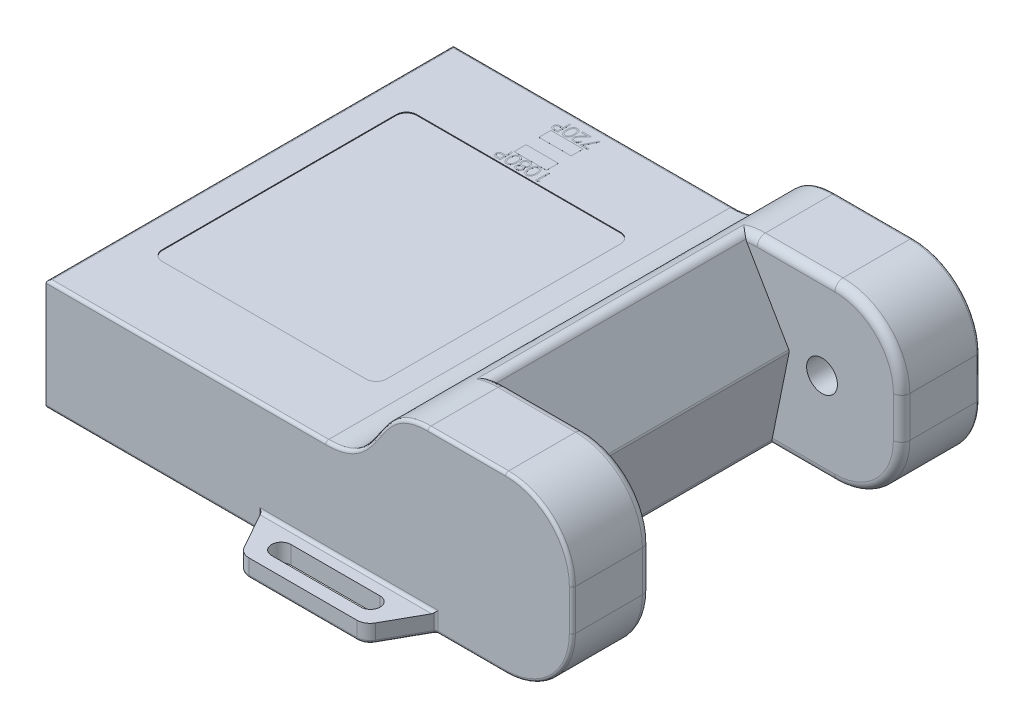
SolidWorks part; units mm, degrees
note: The reader was unsure of these and kept them because the rebuilt part matched: shared geometry of "Sketch4<3>".
ref_plane "Front" through (0, 0, 0) normal (0, 0, 1) x (1, 0, 0)
ref_plane "Top" through (0, 0, 0) normal (0, 1, 0) x (1, 0, 0)
ref_plane "Right" through (0, 0, 0) normal (1, 0, 0) x (0, 0, -1)
sketch "Sketch1" plane through (0, 0, 0) normal (0, 1, 0) x (1, 0, 0)
  line L1 (-26.035, -20.1486) -> (26.035, -20.1486)
  line L2 (-26.035, -20.1486) -> (-26.035, 20.1486)
  line L3 (-26.035, 20.1486) -> (26.035, 20.1486)
  line L4 (26.035, -20.1486) -> (26.035, 20.1486)
  line L5 (-26.035, -20.1486) -> (26.035, 20.1486) construction
  line L6 (-26.035, 20.1486) -> (26.035, -20.1486) construction
  point P0 (0, 0)
  dimension "D1" = 52.07
  dimension "D2" = 40.2971
extrude "Boss-Extrude1" add sketch "Sketch1" along normal mid plane 17.2314
sketch "Sketch2" plane through (0, 0, 20.1486) normal (0, 0, 1) x (1, 0, 0)
  line L0 (-26.035, 2.4079) -> (1.6276, 2.4079)
  line L1 (-26.035, 8.6157) -> (-26.035, -8.6157) construction
  line L2 (-26.035, -8.6157) -> (26.035, -8.6157) construction
  line L3 (-26.035, 8.6157) -> (26.035, 8.6157) construction
  line L4 (26.035, 8.6157) -> (26.035, -8.6157) construction
  spline S0 degree 3 poles (1.6276, 2.4079) (7.5884, 2.4079) (5.8598, 8.6157) (11.7475, 8.6157) knots 0 0 0 0 1 1 1 1
  dimension "D1" = 11.0236
  dimension "D2" = 14.2875
extrude "Cut-Extrude1" cut sketch "Sketch2" against normal through all
fillet "Fillet1" radius 6.604 2 edges at (26.035, -8.6157, 0) (26.035, 8.6157, 0)
sketch "Sketch3" plane through (-26.035, 0, 0) normal (-1, 0, 0) x (0, 0, 1)
  line L0 (20.1486, 2.4079) -> (-20.1485, 2.4079) construction
  line L1 (7.0168, 0.1981) -> (18.4468, 0.1981)
  line L2 (7.0168, 0.1981) -> (7.0168, -3.5357)
  line L3 (7.0168, -3.5357) -> (18.4468, -3.5357)
  line L4 (18.4468, 0.1981) -> (18.4468, -3.5357)
  line L5 (20.1486, 2.4079) -> (20.1486, -8.6157) construction
  dimension "D1" = 11.43
  dimension "D2" = 3.7338
  dimension "D3" = 2.2098
  dimension "D4" = 1.7018
extrude "Cut-Extrude2" cut sketch "Sketch3" against normal blind 2.54
sketch "Sketch4" plane through (-23.495, 0, 0) normal (-1, 0, 0) x (0, 0, 1)
  line L0 (18.4468, 0.1981) -> (7.0168, 0.1981) construction
  line L1 (7.5248, -0.0559) -> (17.9388, -0.0559)
  line L2 (7.5248, -0.0559) -> (7.5248, -3.2817)
  line L3 (7.5248, -3.2817) -> (17.9388, -3.2817)
  line L4 (17.9388, -0.0559) -> (17.9388, -3.2817)
  line L5 (18.4468, 0.1981) -> (7.0168, 0.1981) construction
  line L6 (7.0168, -3.5357) -> (18.4468, -3.5357) construction
  line L7 (8.0328, -0.5639) -> (17.4308, -0.5639)
  line L8 (17.4308, -0.5639) -> (17.4308, -2.7737)
  line L9 (8.0328, -2.7737) -> (17.4308, -2.7737)
  line L10 (8.0328, -0.5639) -> (8.0328, -2.7737)
  line L11 (12.7318, -3.2817) -> (12.7318, -2.7737) construction
  line L12 (15.7917, -2.7737) -> (15.7917, -3.2817)
  line L13 (9.5448, -2.7737) -> (9.6718, -2.7737)
  line L14 (9.5448, -2.7737) -> (9.5448, -3.2817)
  line L15 (9.5448, -3.2817) -> (9.6718, -3.2817)
  line L16 (9.6718, -2.7737) -> (9.6718, -3.2817)
  line L17 (15.9187, -3.2817) -> (15.7917, -3.2817)
  line L18 (15.9187, -2.7737) -> (15.9187, -3.2817)
  line L19 (15.9187, -2.7737) -> (15.7917, -2.7737)
  point P4 (12.7318, -0.0559)
  point P7 (12.7318, 0.1981)
  point P22 (9.6718, -3.0277)
  dimension "D1" = 10.414
  dimension "D2" = 0.254
  dimension "D3" = 0.254
  dimension "D5" = 0.127
  dimension "D4" = 0.508
extrude "Boss-Extrude2" add sketch "Sketch4" along normal offset from surface (2.4892 mm away) 0.0508 contours L9 L18 L3 L4 L1 L2 L14 L10 L7 L8 | L3 L11 L9 L16 | L11 L3 L12 L9 up to face at (-26.035, -1.6688, 12.7318)
extrude "Boss-Extrude3" add sketch "Sketch4<3>" along normal blind 1.0668 contours L18 L9 L12 L3 | L16 L9 L14 L3
sketch "Sketch4<3>" plane through (-23.495, 0, 0) normal (-1, 0, 0) x (0, 0, 1) same geometry as "Sketch4"
sketch "Sketch6" plane through (-23.495, 0, 0) normal (-1, 0, 0) x (0, 0, 1)
  circle A0 centre (8.8739, -1.9608) radius 0.127
  circle A1 centre (10.1439, -1.9608) radius 0.127
  circle A2 centre (11.4139, -1.9608) radius 0.127
  circle A3 centre (12.6839, -1.9608) radius 0.127
  circle A4 centre (13.9539, -1.9608) radius 0.127
  circle A5 centre (15.2239, -1.9608) radius 0.127
  circle A6 centre (16.4939, -1.9608) radius 0.127
  dimension "D1" = 0.254
  dimension "D2" = 7
extrude "Boss-Extrude4" add sketch "Sketch6" along normal offset from surface (1.524 mm away) 1.016 up to face at (-26.035, -1.6688, 12.7318)
fillet "Fillet2" radius 0.254 4 edges at (-24.7396, -0.0559, 17.9388) (-24.7396, -3.2817, 17.9388) (-24.7396, -3.2817, 7.5248) (-24.7396, -0.0559, 7.5248)
fillet "Fillet3" radius 0.127 4 edges at (-24.765, 0.1981, 18.4468) (-24.765, -3.5357, 18.4468) (-24.765, -3.5357, 7.0168) (-24.765, 0.1981, 7.0168)
sketch "Sketch7" plane through (-26.035, 0, 0) normal (-1, 0, 0) x (0, 0, 1)
  line L0 (-20.1486, -8.6157) -> (20.1486, -8.6157) construction
  line L1 (-3.0226, -5.6693) -> (3.0226, -5.6693)
  line L2 (-3.0226, -5.6693) -> (-3.0226, -2.7991)
  line L3 (-3.0226, -2.7991) -> (3.0226, -2.7991)
  line L4 (3.0226, -5.6693) -> (3.0226, -2.7991)
  line L5 (-3.0226, -5.6693) -> (3.0226, -2.7991) construction
  line L6 (-3.0226, -2.7991) -> (3.0226, -5.6693) construction
  point P0 (0, -4.2342)
  dimension "D1" = 6.0452
  dimension "D2" = 2.8702
  dimension "D3" = 2.9464
extrude "Boss-Extrude5" add sketch "Sketch7" along normal blind 0.8382 separate body
fillet "Fillet4" radius 0.0508 8 edges at (-26.8732, -5.6693, 0) (-26.8732, -4.2342, -3.0226) (-26.8732, -2.7991, 0) (-26.8732, -4.2342, 3.0226) (-26.4541, -2.7991, -3.0226) (-26.4541, -5.6693, 3.0226) (-26.4541, -5.6693, -3.0226) (-26.4541, -2.7991, 3.0226)
sketch "Sketch8" plane through (0, -8.6157, 0) normal (0, -1, 0) x (1, 0, 0)
  line L0 (-26.035, 20.1486) -> (19.431, 20.1486) construction
  line L1 (-2.1844, 24.6951) -> (10.033, 24.6951)
  line L2 (-2.1844, 24.6951) -> (-2.1844, 20.1486)
  line L3 (-2.1844, 20.1486) -> (10.033, 20.1486)
  line L4 (10.033, 24.6951) -> (10.033, 20.1486)
  line L5 (-2.1844, 24.6951) -> (-4.7244, 20.1486)
  line L6 (3.9243, 24.6951) -> (3.9243, 20.1486) construction
  line L7 (-4.7244, 20.1486) -> (-2.1844, 20.1486)
  line L8 (12.573, 20.1486) -> (10.033, 20.1486)
  line L9 (10.033, 24.6951) -> (12.573, 20.1486)
  line L10 (26.035, 20.1486) -> (26.035, -20.1486) construction
  line L11 (-0.489, 22.4218) -> (8.3375, 22.4218) construction
  line L12 (-0.489, 23.3744) -> (8.3375, 23.3744)
  line L13 (-0.489, 21.4693) -> (8.3375, 21.4693)
  line L14 (0, 0) -> (26.035, 0) construction
  line L15 (-2.1844, 24.6951) -> (-4.7244, 20.1486)
  line L16 (-4.7244, 20.1486) -> (-2.1844, 20.1486)
  line L17 (12.573, 20.1486) -> (10.033, 20.1486)
  line L18 (10.033, 24.6951) -> (12.573, 20.1486)
  line L19 (-2.1844, 24.6951) -> (-2.1844, 20.1486)
  line L20 (10.033, 24.6951) -> (10.033, 20.1486)
  line L21 (12.573, 20.1486) -> (10.033, 20.1486)
  line L22 (10.033, 24.6951) -> (12.573, 20.1486)
  line L23 (-2.1844, 24.6951) -> (-2.1844, 20.1486)
  line L24 (10.033, 24.6951) -> (10.033, 20.1486)
  line L25 (-2.1844, 24.6951) -> (-4.7244, 20.1486)
  line L26 (-4.7244, 20.1486) -> (-2.1844, 20.1486)
  line L27 (-2.1844, 24.6951) -> (-4.7244, 20.1486)
  line L28 (-4.7244, 20.1486) -> (-2.1844, 20.1486)
  line L29 (-2.1844, 24.6951) -> (-2.1844, 20.1486)
  line L30 (10.033, 24.6951) -> (10.033, 20.1486)
  arc A0 (-0.489, 23.3744) -> (-0.489, 21.4693) centre (-0.489, 22.4218) ccw
  arc A1 (8.3375, 21.4693) -> (8.3375, 23.3744) centre (8.3375, 22.4218) ccw
  point P14 (3.9243, 22.4218)
  point P19 (9.29, 22.4218)
  point P20 (-1.4415, 22.4218)
  line M9 (19.431, 20.1486) -> (-26.035, 20.1486)
  dimension "D1" = 4.5466
  dimension "D2" = 12.2174
  dimension "D3" = 2.54
  dimension "D4" = 13.462
  dimension "D5" = 10.7315
  dimension "D6" = 1.905
extrude "Boss-Extrude6" add sketch "Sketch8" against normal blind 1.778 contours L2 L5 M9 | L4 L1 L2 A1 L13 A0 L12 M9 | L9 L4 M9
mirror "Mirror1" about plane through (0, 0, 0) normal (0, 0, 1) of "Boss-Extrude6"
fillet "Fillet5" radius 1.3208 4 edges at (-2.1844, -7.7267, -24.6951) (10.033, -7.7267, -24.6951) (-2.1844, -7.7267, 24.6951) (10.033, -7.7267, 24.6951)
fillet "Fillet6" radius 0.3048 6 edges at (12.573, -7.7267, -20.1486) (3.9243, -6.8377, -20.1486) (-4.7244, -7.7267, -20.1486) (12.573, -7.7267, 20.1486) (-4.7244, -7.7267, 20.1486) (3.9243, -6.8377, 20.1486)
sketch "Sketch9" plane through (0, 8.6157, 0) normal (0, 1, 0) x (1, 0, 0)
  line L0 (26.035, 20.1486) -> (26.035, -20.1486) construction
  line L1 (26.035, 12.4143) -> (14.9352, 12.4142)
  line L2 (26.035, 12.4143) -> (26.035, -12.4143)
  line L3 (26.035, -12.4143) -> (14.9352, -12.4142)
  line L4 (14.9352, 12.4142) -> (14.9352, -12.4142)
  line L5 (11.7475, -20.1486) -> (11.7475, 20.1485) construction
  line L6 (26.035, 20.1486) -> (19.431, 20.1486) construction
  point P6 (14.9352, 0)
  point P9 (11.7475, 0)
  dimension "D1" = 7.7343
  dimension "D2" = 11.0998
extrude "Cut-Extrude3" cut sketch "Sketch9" against normal up to next
sketch "Sketch10" plane through (0, 0, -12.4142) normal (0, 0, 1) x (1, 0, 0)
  line L0 (14.9352, 0.4877) -> (10.287, 8.4639)
  line L1 (14.9352, -8.6157) -> (14.9352, 8.6157) construction
  line L2 (19.431, 8.6157) -> (14.9352, 8.6157) construction
  line L3 (26.035, 2.0117) -> (26.035, -2.0117) construction
  line L4 (14.9352, 0.4877) -> (14.9352, 8.6157)
  line L5 (14.9352, 0.4877) -> (13.081, -8.6157)
  line L6 (-26.035, -8.6157) -> (-4.9033, -8.6157) construction
  line L7 (10.287, 8.4639) -> (10.287, 11.5298)
  line L8 (10.287, 11.5298) -> (14.9352, 11.5298)
  line L9 (14.9352, 8.4639) -> (14.9352, 11.5298)
  line L10 (-26.035, 2.4079) -> (-26.035, -8.6157) construction
  line L11 (14.9352, 0.4877) -> (14.9352, -8.6157)
  line L14 (13.081, -8.6157) -> (13.081, -10.4697)
  line L15 (13.081, -10.4697) -> (14.9352, -10.4697)
  line L16 (14.9352, -8.6157) -> (14.9352, -10.4697)
  spline S0 degree 3 poles (1.6276, 2.4079) (7.5884, 2.4079) (5.8598, 8.6157) (11.7475, 8.6157) knots 0 0 0 0 1 1 1 1 construction
  line M8 (14.9352, 8.6157) -> (14.9352, -8.6157)
  dimension "D1" = 8.128
  dimension "D2" = 15.748
  dimension "D3" = 39.116
extrude "Cut-Extrude4" cut sketch "Sketch10" along normal up to surface (24.8285 mm away) contours L9 L8 L7 L0 L4 M8 | L16 L5 L14 L15 M8 up to face at (20.5896, 0, 12.4143)
fillet "Fillet7" radius 0.8128 14 edges at (13.081, -8.6157, 0) (10.287, 8.4639, 0) (16.256, -8.6157, 12.4143) (24.1007, -6.6814, 12.4143) (26.035, 0, 12.4143) (24.1007, 6.6814, 12.4143) (16.256, -8.6157, -12.4142) (24.1007, -6.6814, -12.4142) (26.035, 0, -12.4143) (24.1007, 6.6814, -12.4142) (15.5892, 8.6157, 12.4143) (15.5892, 8.6157, -12.4142)
fillet "Fillet8" radius 0.3048 1 edges at (14.9352, 0.4877, 0)
fillet "Fillet9" radius 0.3048 32 edges at (15.5892, 8.6157, 20.1486) (-12.2037, 2.4079, -20.1485) (-12.2037, 2.4079, 20.1486) (-26.035, 2.4079, 0) (26.035, 0, -20.1486) (26.035, 0, 20.1486) (15.5892, 8.6157, -20.1485) (3.9243, -8.6157, -24.6951) (11.4484, -8.6157, 22.1616) (3.9243, -8.6157, 24.6951) (16.0914, -8.6157, -20.1486) (-3.5998, -8.6157, 22.1616) (-3.5998, -8.6157, -22.1616) (11.4484, -8.6157, -22.1616) (9.9264, -8.6157, 24.5135) (24.1007, 6.6814, -20.1486) (-2.0778, -8.6157, 24.5135) (-2.0778, -8.6157, -24.5135) (9.9264, -8.6157, -24.5135) (24.1007, -6.6814, -20.1486) (24.1007, 6.6814, 20.1486) (24.1007, -6.6814, 20.1486) (-15.4691, -8.6157, -20.1486) (16.0914, -8.6157, 20.1486) (12.5976, -8.6157, -20.1905) (-4.749, -8.6157, -20.1905) (12.5976, -8.6157, 20.1905) (-4.749, -8.6157, 20.1905) (-15.4691, -8.6157, 20.1486) (-26.035, -8.6157, 0)
sketch "Sketch11" plane through (0, 0, 0) normal (0, 0, 1) x (1, 0, 0)
  line L0 (26.035, 2.0117) -> (26.035, -2.0117) construction
  line L1 (25.7302, -2.0117) -> (25.7302, 2.0117) construction
  circle A0 centre (18.161, 0) radius 1.524
  point P6 (25.7302, 0)
  dimension "D1" = 3.048
  dimension "D2" = 7.874
extrude "Cut-Extrude5" cut sketch "Sketch11" against normal offset from surface 2.54 and the other way offset from surface (14.9543 mm away) 2.54 up to face at (17.5268, 0.9697, -12.4142) offset beyond the face yes other way up to face at (17.4126, 0.9607, 12.4142)
sketch "Sketch12" plane through (0, 2.4079, 0) normal (0, 1, 0) x (1, 0, 0)
  line L0 (-26.035, 20.1486) -> (1.6276, 20.1486) construction
  line L1 (-13.8557, 17.6086) -> (-10.6553, 17.6086)
  line L2 (-13.8557, 17.6086) -> (-13.8557, 16.4275)
  line L3 (-13.8557, 16.4275) -> (-10.6553, 16.4275)
  line L4 (-10.6553, 17.6086) -> (-10.6553, 16.4275)
  line L5 (-13.8557, 15.1574) -> (-10.6553, 15.1574)
  line L6 (-13.8557, 15.1574) -> (-13.8557, 13.9763)
  line L7 (-13.8557, 13.9763) -> (-10.6553, 13.9763)
  line L8 (-10.6553, 15.1574) -> (-10.6553, 13.9763)
  line L9 (-26.035, -20.1486) -> (-26.035, 20.1486) construction
  dimension "D1" = 1.1811
  dimension "D2" = 3.2004
  dimension "D3" = 2.54
  dimension "D4" = 12.1793
  dimension "D5" = 1.27
extrude "LEDs" add sketch "Sketch12" along normal blind 0.0025 separate body
sketch "Sketch13" plane through (0, 2.4079, 0) normal (0, 1, 0) x (1, 0, 0)
  line L0 (1.6276, -20.1486) -> (-26.035, -20.1486) construction
  line L1 (-22.86, -12.8334) -> (-0.6858, -12.8334)
  line L2 (-22.86, -12.8334) -> (-22.86, 12.338)
  line L3 (-22.86, 12.338) -> (-0.6858, 12.338)
  line L4 (-0.6858, -12.8334) -> (-0.6858, 12.338)
  line L5 (-22.86, -12.8334) -> (-0.6858, 12.338) construction
  line L6 (-22.86, 12.338) -> (-0.6858, -12.8334) construction
  line L7 (-26.035, -20.1486) -> (-26.035, 20.1486) construction
  point P0 (-11.7729, -0.2477)
  dimension "D1" = 22.1742
  dimension "D2" = 25.1714
  dimension "D3" = 7.3152
  dimension "D4" = 3.175
extrude "Cut-Extrude6" cut sketch "Sketch13" against normal blind 0.0762 contours L2 L3 L4 L1
sketch "Sketch14" plane through (0, 2.4079, 0) normal (0, 1, 0) x (1, 0, 0)
  line L0 (-17.0608, 13.8493) -> (-7.4502, 13.8493) construction
  line L2 (-10.6553, 15.1574) -> (-13.8557, 15.1574) construction
  line L3 (-13.8557, 13.9763) -> (-10.6553, 13.9763) construction
  line L4 (-17.8385, 19.0563) -> (-6.6725, 19.0563) construction
  line L5 (-10.6553, 17.6086) -> (-13.8557, 17.6086) construction
  text T0 "1080P" font "Century Gothic" height 1.27
  text T1 "720P" font "Century Gothic" height 1.27
  point P4 (-12.2555, 19.0563)
  point P5 (-12.2555, 13.8493)
  point P8 (-12.2555, 15.1574)
  point P15 (-12.2555, 17.6086)
  dimension "D1" = 0.127
  dimension "D2" = 1.4478
extrude "Boss-Extrude8" add sketch "Sketch14" along normal blind 0.0025
fillet "Fillet10" radius 1.016 4 edges at (-0.6858, 2.3698, 12.8334) (-0.6858, 2.3698, -12.338) (-22.86, 2.3698, 12.8334) (-22.86, 2.3698, -12.338)
